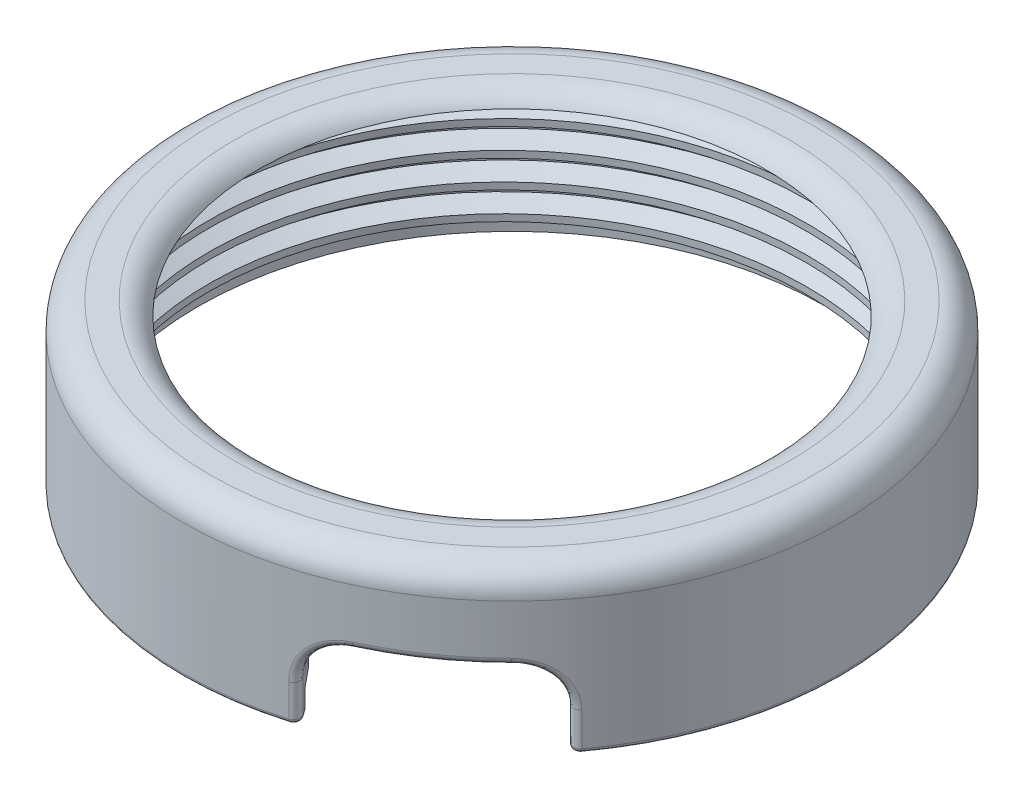
SolidWorks part; units mm, degrees
ref_plane "Front Plane" through (0, 0, 0) normal (0, 0, 1) x (1, 0, 0)
ref_plane "Top Plane" through (0, 0, 0) normal (0, 1, 0) x (1, 0, 0)
ref_plane "Right Plane" through (0, 0, 0) normal (1, 0, 0) x (0, 0, -1)
sketch "Sketch1" plane through (0, 0, 0) normal (0, 1, 0) x (1, 0, 0)
  circle A0 centre (0, 0) radius 24
  dimension "D1" = 48
extrude "Boss-Extrude1" add sketch "Sketch1" along normal blind 11.8
sketch "Sketch2" plane through (0, 11.8, 0) normal (0, 1, 0) x (1, 0, 0)
  circle A0 centre (0, 0) radius 22.85
  dimension "D1" = 45.7
extrude "Cut-Extrude1" cut sketch "Sketch2" against normal up to next from offset 1 offset against normal yes
sketch "Sketch3" plane through (0, 11.8, 0) normal (0, 1, 0) x (1, 0, 0)
  circle A0 centre (0, 0) radius 18.5
  dimension "D1" = 37
extrude "Cut-Extrude2" cut sketch "Sketch3" against normal up to next
thread "Thread1" pitch 2 method extrude profile "Thread Profile1" start angle 0, offset 0, length 0, pitch 2, diameter 45.7
ref_plane "Plane1" through (22.85, 0, 0) normal (0, 0, 1) x (1, 0, 0)
sketch "Thread Profile1" plane through (22.85, 0, 0) normal (0, 0, 1) x (1, 0, 0)
  line L0 (0, 0) -> (0, 2) construction
  line L11 (0, 0) -> (0, 1.75)
  line L12 (0, 1.75) -> (-1.0825, 1.125)
  line L13 (-1.0825, 1.125) -> (-1.0825, 0.625)
  line L15 (-1.0825, 0.625) -> (0, 0)
  line L17 (-1.0825, 0.875) -> (0, 0.875) construction
  point P2 (0, 0)
  dimension "Pitch" = 2
  dimension "Profile_Angle" = 60
  dimension "Profile_Land" = 0.5
  dimension "Profile_Height" = 1.0825
sketch "Sketch6" plane through (0, 11.8, 0) normal (0, 1, 0) x (1, 0, 0)
  circle A0 centre (0, 0) radius 24
extrude "Cut-Extrude3" cut sketch "Sketch6" along normal blind 2
fillet "Fillet1" radius 2 1 edges at (0, 11.8, 24)
fillet "Fillet2" radius 2 1 edges at (0, 11.8, 18.5)
ref_plane "Plane2" through (13.7658, 0, 19.6596) normal (-0.5736, 0, -0.8192) x (0, -1, 0)
sketch "Sketch9" plane through (13.7658, 0, 19.6596) normal (-0.5736, 0, -0.8192) x (0, -1, 0)
  line L0 (0, -7) -> (0, 7)
  line L1 (0, -24) -> (0, 24) construction
  line L2 (0, -7) -> (-2.75, -7)
  line L4 (-2.64, 7) -> (0, 7)
  line L5 (-5.7, -4.05) -> (-5.7, 4.0521)
  arc A0 (-2.75, -7) -> (-5.7, -4.05) centre (-2.75, -4.05) cw
  arc A1 (-2.64, 7) -> (-5.7, 4.0521) centre (-2.75, 4.0521) ccw
  dimension "D3" = 2.95
  dimension "D4" = 2.95
  dimension "D1" = 14
  dimension "D2" = 2.64
  dimension "D5" = 5.7
  dimension "D6" = 2.95
extrude "Cut-Extrude4" cut sketch "Sketch9" along normal up to next
fillet "Fillet3" radius 0.5 5 edges at (7.9613, 4.4473, 22.6411) (13.765, 5.7, 19.6602) (18.1874, 5.0346, 15.6594) (7.4332, 1.32, 22.8199) (18.9014, 1.375, 14.7898)
fillet "Fillet4" radius 0.3 5 edges at (18.3592, 0, 14.0155) (18.9117, 0, 14.4415) (6.8911, 0, 22.0456) (7.1024, 0, 22.7105) (-13.7658, 0, -19.6596)
